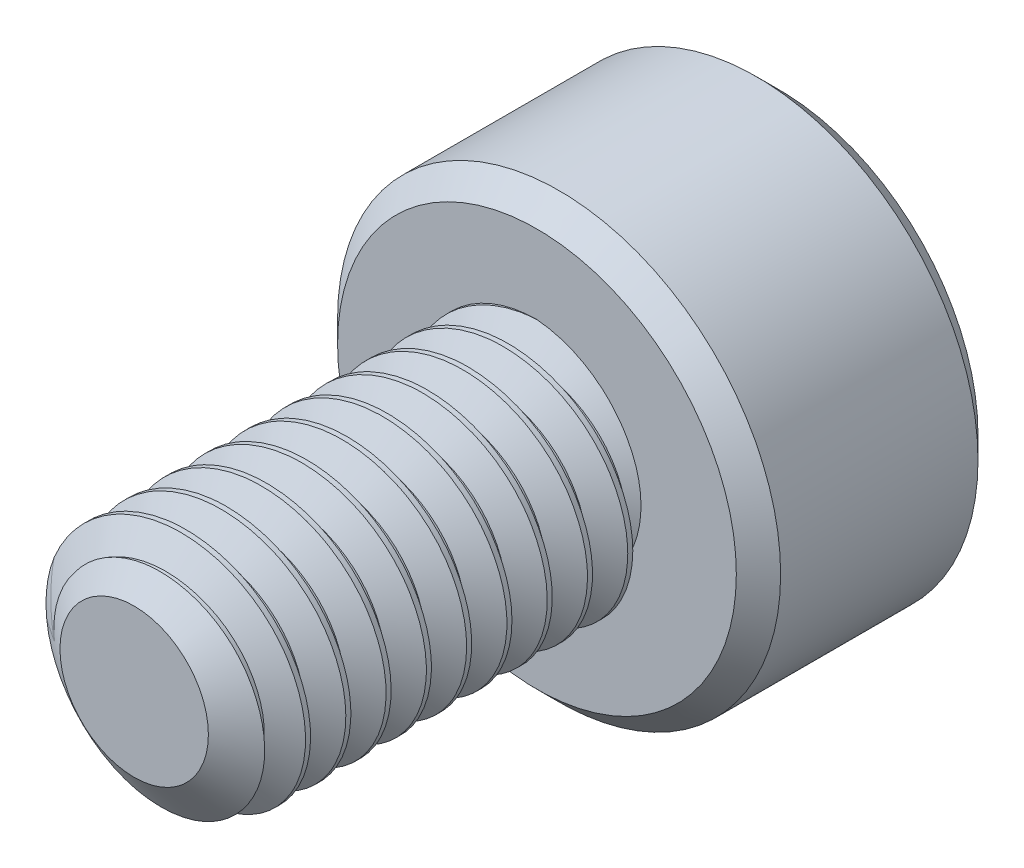
SolidWorks part; units mm, degrees
material "Plain Carbon Steel"
ref_plane "Front Plane" through (0, 0, 0) normal (0, 0, 1) x (1, 0, 0)
ref_plane "Top Plane" through (0, 0, 0) normal (0, 1, 0) x (1, 0, 0)
ref_plane "Right Plane" through (0, 0, 0) normal (1, 0, 0) x (0, 0, -1)
sketch "Sketch1" plane through (0, 0, 0) normal (0, 0, 1) x (1, 0, 0)
  circle A0 centre (0, 0) radius 1.5
  dimension "OD" = 3
extrude "Extrude1" add sketch "Sketch1" against normal blind 5
sketch "Sketch2" plane through (0, 0, 0) normal (0, 0, 1) x (1, 0, 0)
  circle A0 centre (0, 0) radius 1.5 construction
  circle A1 centre (0, 0) radius 1.5
curve "Helix/Spiral1" pitch 0.5 height 5.5 radius 1.5 centre (0, 0, 0) axis (0, 0, -1) start towards (0, 1, 0) parameters "pitch"=0.5
sketch "Sketch3" plane through (0, 0, 0) normal (1, 0, 0) x (0, 0, -1)
  line L0 (-0.4375, 1.5) -> (-0.25, 1.1752)
  line L1 (-0.25, 1.1752) -> (-0.1875, 1.1752)
  line L2 (-0.1875, 1.1752) -> (0, 1.5)
  line L3 (-0.4375, 1.5) -> (0, 1.5)
  line L4 (-0.2187, 1.5) -> (-0.2187, 1.1752) construction
  line L5 (-0.3437, 1.3376) -> (-0.0937, 1.3376) construction
  line L6 (0, 1.5) -> (0, -1.5) construction
  dimension "D1" = 0.0625
  dimension "D2" = 0.25
  dimension "D3" = 60
sweep "Cut-Sweep1" cut profiles "Sketch3" path "Helix/Spiral1"
sketch "Sketch4" plane through (0, 0, 0) normal (1, 0, 0) x (0, 0, -1)
  line L0 (0.4053, 1.5) -> (0, 0.9212)
  line L1 (0, 0.9212) -> (0, 1.5)
  line L2 (0.4053, 1.5) -> (0, 1.5)
  line L3 (-0.4375, 1.5) -> (0, 1.5) construction
  line L4 (0, 0) -> (7.0209, 0) construction
  dimension "D1" = 55
  dimension "D2" = 0.254
revolve "Cut-Revolve1" cut sketch "Sketch4" angle 360 about L4
sketch "Sketch5" plane through (0, 0, 0) normal (1, 0, 0) x (0, 0, -1)
  line L0 (5, -1.1822) -> (5, 1.0703) construction
  line L1 (5, 1.627) -> (87.4327, 1.627)
  line L2 (5, 1.627) -> (5, 0)
  line L3 (5, 0) -> (87.3125, 0)
  line L4 (87.3125, 1.2968) -> (87.3125, 0)
  line L5 (87.4327, 1.627) -> (87.3125, 1.2968)
  line L6 (0, 0) -> (9.9695, 0) construction
  point P3 (87.3125, 1.627)
  point P10 (87.3125, 1.627)
  dimension "D1" = 0.3302
  dimension "Thread min" = 87.3125
  dimension "D2" = 0.127
  dimension "D3" = 20
revolve "partially thread" [suppressed] add sketch "Sketch5" angle 360 about L6
sketch "Sketch6" plane through (0, 0, -5) normal (0, 0, -1) x (-1, 0, 0)
  circle A0 centre (0, 0) radius 2.75
  dimension "head dia" = 5.5
extrude "Extrude2" add sketch "Sketch6" along normal blind 3
sketch "Sketch7" plane through (0, 0, -8) normal (0, 0, -1) x (-1, 0, 0)
  line L1 (0, 1.4434) -> (-1.25, 0.7217)
  line L2 (-1.25, 0.7217) -> (-1.25, -0.7217)
  line L3 (-1.25, -0.7217) -> (0, -1.4434)
  line L4 (0, -1.4434) -> (1.25, -0.7217)
  line L5 (1.25, -0.7217) -> (1.25, 0.7217)
  line L6 (1.25, 0.7217) -> (0, 1.4434)
  circle A0 centre (0, 0) radius 1.25 construction
  dimension "hex dia" = 2.5
extrude "Cut-Extrude1" cut sketch "Sketch7" against normal blind 1.875
sketch "Sketch8" plane through (0, 0, -8) normal (0, 0, -1) x (-1, 0, 0)
  circle A0 centre (0, 0) radius 1.4434
extrude "Cut-Extrude2" cut sketch "Sketch8" against normal through all draft 45
chamfer "Chamfer1" distance 0.275 angle 45 2 edges at (-2.75, 0, -8) (-2.75, 0, -5)
sketch "Sketch9" plane through (0, 0, 0) normal (1, 0, 0) x (0, 0, -1)
  line L0 (0, 1.5) -> (0, -1.5) construction
  line L1 (2.75, 1.5) -> (2.75, -1.5) construction
  dimension "D1" = 2.75
  dimension "D4" = 0.635
  dimension "D5" = 0.3302
equation "\"D3@Helix/Spiral1\" = \"screw length@Extrude1\"+\"pitch@Helix/Spiral1\""
equation "\"D1@Sketch3\" = \"pitch@Helix/Spiral1\"*.125"
equation "\"D2@Sketch3\" = \"pitch@Helix/Spiral1\"*.5"
equation "\"D1@Cut-Extrude1\" = \"hex dia@Sketch7\"*.75"
equation "\"D1@Chamfer1\" = \"head dia@Sketch6\"*.05"
equation "\"D1@Sketch9\" = \"pitch@Helix/Spiral1\"*5.5"
